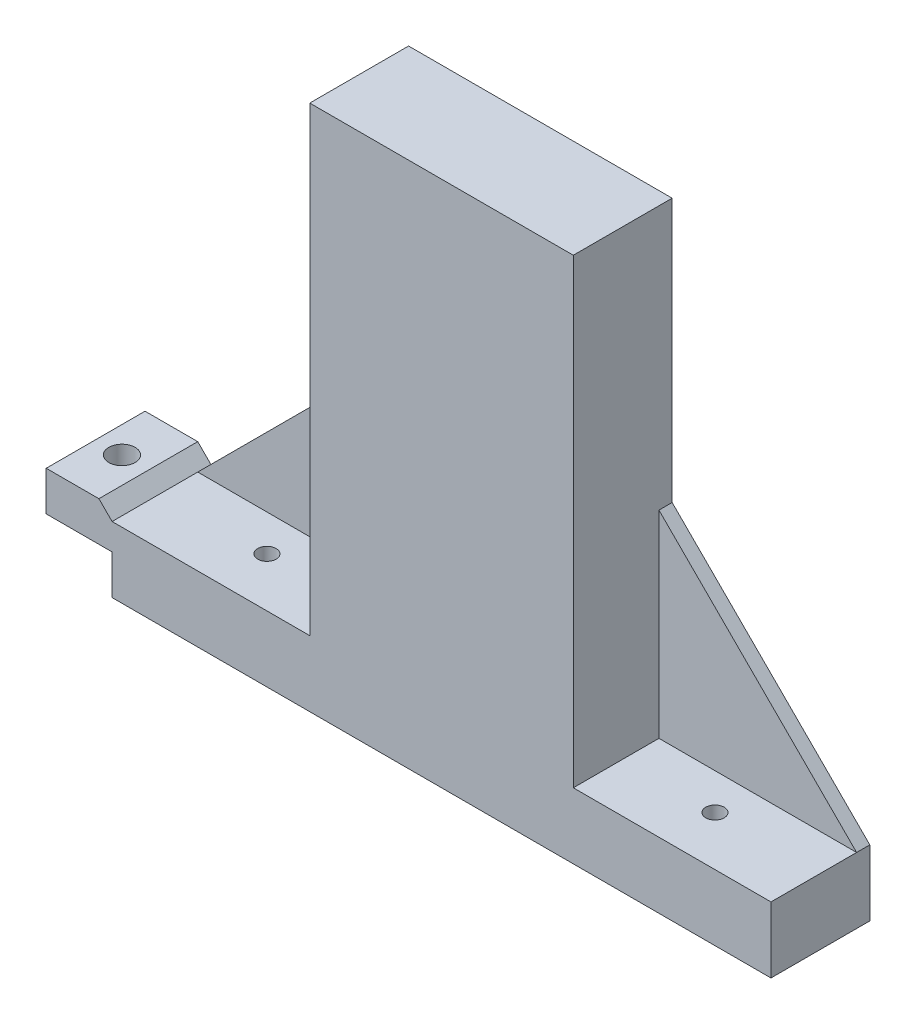
SolidWorks part; units mm, degrees
ref_plane "前基準面" through (0, 0, 0) normal (0, 0, 1) x (1, 0, 0)
ref_plane "上基準面" through (0, 0, 0) normal (0, 1, 0) x (1, 0, 0)
ref_plane "右基準面" through (0, 0, 0) normal (1, 0, 0) x (0, 0, -1)
sketch "草圖2" plane through (0, 0, 0) normal (0, 1, 0) x (1, 0, 0)
  line L5 (-50, 7.5) -> (50, 7.5)
  line L6 (-50, 7.5) -> (-50, -7.5)
  line L7 (-50, -7.5) -> (50, -7.5)
  line L8 (50, 7.5) -> (50, -7.5)
  line L9 (0, -7.5) -> (0, 7.5) construction
  line L10 (-50, 0) -> (50, 0) construction
  circle A4 centre (-34, 0) radius 1.4
  circle A5 centre (34, 0) radius 1.4
  point P0 (0, 0)
  dimension "D3" = 68
  dimension "D2" = 2.8
  dimension "D1" = 100
  dimension "D4" = 15
extrude "填料-伸長1" add sketch "草圖2" along normal blind 10
sketch "草圖3" plane through (0, 10, 0) normal (0, 1, 0) x (1, 0, 0)
  line L0 (-50, -7.5) -> (50, -7.5) construction
  line L1 (-20, 7.5) -> (20, 7.5)
  line L2 (-20, 7.5) -> (-20, -7.5)
  line L3 (-20, -7.5) -> (20, -7.5)
  line L4 (20, 7.5) -> (20, -7.5)
  line L5 (0, -7.5) -> (0, 7.5) construction
  line L6 (-20, 0) -> (20, 0) construction
  line L7 (-50, 7.5) -> (-50, -7.5) construction
  point P0 (0, 0)
  point P6 (-34, 0)
  point P7 (34, 0)
  dimension "D1" = 30
  dimension "D2" = 14
extrude "填料-伸長2" add sketch "草圖3" along normal blind 70
sketch "草圖5" plane through (0, 0, -7.5) normal (0, 0, -1) x (-1, 0, 0)
  line L0 (-50, 10) -> (-20, 40)
  line L1 (-20, 80) -> (-20, 10) construction
  line L2 (-20, 40) -> (-20, 10)
  line L3 (-20, 10) -> (-50, 10)
  line L4 (0, 0) -> (0, 43.0538) construction
  line L5 (-50, 0) -> (50, 0) construction
  line L6 (20, 40) -> (20, 10)
  line L7 (50, 10) -> (20, 40)
  line L8 (20, 10) -> (50, 10)
  dimension "D1" = 45
extrude "填料-伸長3" add sketch "草圖5" against normal blind 2
sketch "草圖6" plane through (0, 0, 7.5) normal (0, 0, 1) x (1, 0, 0)
  line L0 (-50, 6) -> (-60, 6)
  line L2 (-50, 12) -> (-50, 6)
  line L3 (-50, 12) -> (-60, 12)
  line L4 (-60, 12) -> (-60, 6)
  line L5 (-50, 0) -> (50, 0) construction
  line L6 (-50, 10) -> (-50, 0) construction
  dimension "D1" = 10
  dimension "D2" = 6
  dimension "D3" = 6
extrude "填料-伸長4" add sketch "草圖6" against normal up to surface (15 mm away) up to face at (0, 32.5, -7.5)
sketch "草圖7" plane through (0, 10, 0) normal (0, 1, 0) x (1, 0, 0)
  line L3 (-60, 7.5) -> (-60, -7.5) construction
  circle A0 centre (-56, 0) radius 2
  dimension "D1" = 4
  dimension "D2" = 4
extrude "除料-伸長1" cut sketch "草圖7" against normal through all both and the other way through all
chamfer "導角1" distance 2 angle 45 1 edges at (-50, 12, 0)
